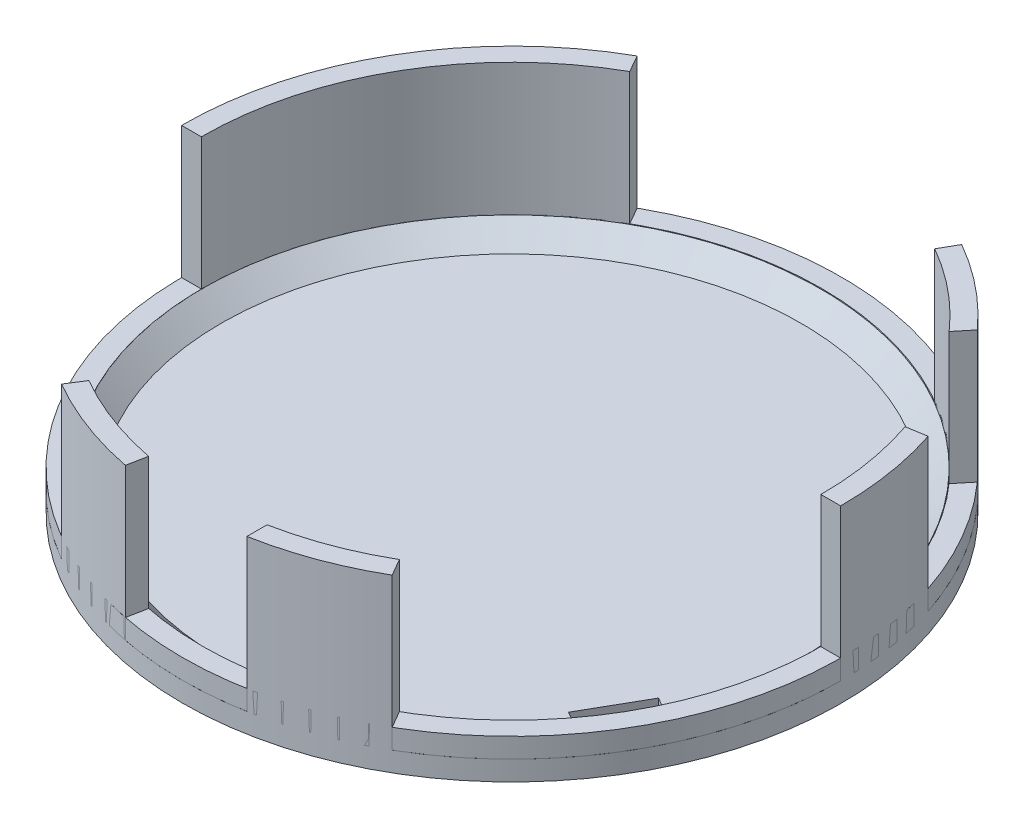
SolidWorks part; units mm, degrees
ref_plane "Front Plane" through (0, 0, 0) normal (0, 0, 1) x (1, 0, 0)
ref_plane "Top Plane" through (0, 0, 0) normal (0, 1, 0) x (1, 0, 0)
ref_plane "Right Plane" through (0, 0, 0) normal (1, 0, 0) x (0, 0, -1)
sketch "Sketch1" plane through (0, 0, 0) normal (0, 1, 0) x (1, 0, 0)
  circle A0 centre (0, 0) radius 25
extrude "Boss-Extrude1" add sketch "Sketch1" along normal blind 1.5
sketch "Sketch3" plane through (0, 1.5, 0) normal (0, 1, 0) x (1, 0, 0)
  line L0 (0, 0) -> (-16.5621, -18.7269)
  circle A0 centre (0, 0) radius 25 construction
  circle A1 centre (0, 0) radius 25
  circle A2 centre (0, 0) radius 23.5
extrude "Boss-Extrude2" add sketch "Sketch3" along normal blind 11.5 contours A2 A1 region at (-9.9796, 1.5, -22.1484)
sketch "Sketch4" plane through (0, 1.5, 0) normal (0, 1, 0) x (1, 0, 0)
  line L12 (12.5369, -21.6293) -> (11.7268, -20.2317)
  line L13 (-12.5582, -21.6169) -> (-11.692, -20.2518)
  line L14 (23.3845, -0.0671) -> (24.9999, -0.0671)
  line L15 (11.6192, 20.2937) -> (12.4219, 21.6955)
  line L16 (-11.4849, 20.37) -> (-12.2782, 21.7772)
  line L17 (-23.3845, -0.0671) -> (-24.9999, -0.0671)
  line L18 (4.4842, -24.5945) -> (4.4842, -22.9506)
  line L20 (-4.4866, -22.9501) -> (-4.7966, -24.5355)
  line L21 (22.1294, 7.5584) -> (23.7437, 7.8254)
  line L23 (17.5844, 15.4152) -> (18.6211, 16.681)
  circle A1 centre (0, 0) radius 23.3846
  circle A2 centre (0, 0) radius 25
  circle M13 centre (0, 0) radius 23.5
extrude "Cut-Extrude3" cut sketch "Sketch4" against normal blind 0.001 and the other way blind 15 contours L12 A2 L14 M13 | L20 A2 L18 M13 | L21 A2 L23 M13 | L15 A2 L16 M13 | L17 A2 L13 M13 region at (12.3796, 1.5, 20.8536) region at (-0.0856, 1.5, 24.1088) region at (-21.4316, 1.5, 12.3735) region at (20.8613, 1.5, -12.0676) region at (0.0818, 1.5, -24.7486)
sketch "Sketch5" plane through (0, 0, 0) normal (0, -1, 0) x (1, 0, 0)
  line L0 (0, 0) -> (18.8419, 10.7717)
  line L1 (12.6838, 21.5435) -> (25, 0)
  line L2 (18.8419, 10.7717) -> (21.7036, 12.4078)
  line L3 (18.8419, 10.7717) -> (17.6008, 12.9427)
  line L8 (17.6008, 12.9427) -> (18.4777, 13.444)
  line L9 (18.4777, 13.444) -> (20.9605, 9.1011)
  line L10 (20.9605, 9.1011) -> (19.2165, 8.1041)
  line L11 (19.2165, 8.1041) -> (16.7337, 12.447)
  line L12 (16.7337, 12.447) -> (17.6008, 12.9427)
  line L13 (55.1315, -18.0689) -> (16.7337, -26.7785)
  circle A0 centre (0, 0) radius 25 construction
extrude "Cut-Extrude4" cut sketch "Sketch5" against normal blind 5.001 contours L12 L11 L0 L1 | L9 L8 L1 L2 | L10 L9 L2 L1 | L11 L10 L1 L0 region at (17.7878, 0, 11.6094) region at (19.0292, 0, 9.4379) region at (19.9012, 0, 9.9364) region at (18.6598, 0, 12.1079)
sketch "Sketch8" plane through (0, 0, 0.0671) normal (0, 0, 1) x (1, 0, 0)
  line L0 (-23.4999, 1.5) -> (-23.4999, 3)
  line L1 (-23.4999, 1.5) -> (-23.4999, 13) construction
  line L2 (-23.4999, 1.5) -> (-21.9999, 1.5)
  line L3 (-23.4999, 3) -> (-21.9999, 1.5)
  line L4 (0, 0) -> (0, 7.9293)
revolve "Revolve4" add sketch "Sketch8" angle 360 about L4 region at (-22.9999, 2, 0.0671)
sketch "Sketch9" plane through (0, 1.5, 0) normal (0, 1, 0) x (1, 0, 0)
  circle A0 centre (0, 0) radius 23.5
  circle A1 centre (0, 0) radius 25
extrude "Boss-Extrude4" add sketch "Sketch9" along normal blind 1.5 separate body
sketch "Sketch10" plane through (0, 0, 0) normal (0, -1, 0) x (1, 0, 0)
  line L0 (19.2165, 8.1041) -> (20.9605, 9.1011)
  line L1 (20.9605, 9.1011) -> (18.4777, 13.444)
  line L2 (18.4777, 13.444) -> (20.9605, 9.1011) construction
  line L3 (18.4777, 13.444) -> (16.7337, 12.447)
  line L4 (16.7337, 12.447) -> (19.2165, 8.1041)
extrude "Cut-Extrude5" cut sketch "Sketch10" against normal blind 4.5
sketch "Sketch11" plane through (0, 3, 0) normal (0, 1, 0) x (1, 0, 0)
  line L0 (-23.5, 0) -> (-23.3276, -2.8414)
  line L1 (-23.3276, -2.8414) -> (-24.8274, -2.9324)
  line L2 (-24.8274, -2.9324) -> (-25, 0)
  circle A0 centre (0, 0) radius 23.5 construction
  circle A1 centre (0, 0) radius 25 construction
  circle A2 centre (0, 0) radius 25
